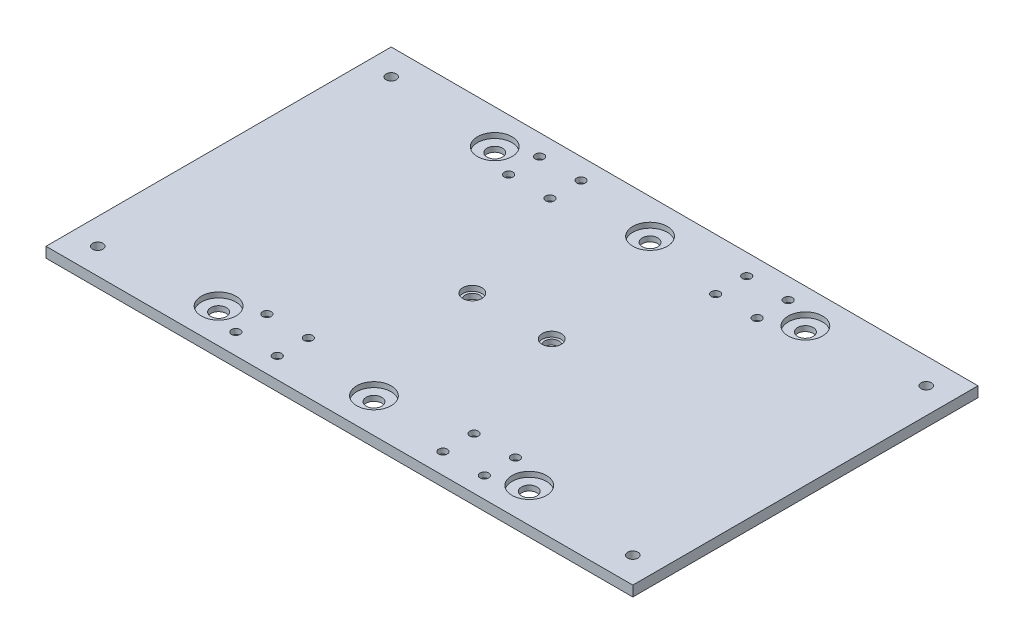
SolidWorks part; units mm, degrees
ref_plane "Front Plane" through (0, 0, 0) normal (0, 0, 1) x (1, 0, 0)
ref_plane "Top Plane" through (0, 0, 0) normal (0, 1, 0) x (1, 0, 0)
ref_plane "Right Plane" through (0, 0, 0) normal (1, 0, 0) x (0, 0, -1)
sketch "Sketch1" plane through (0, 0, 0) normal (0, 1, 0) x (1, 0, 0)
  line L0 (-1000, 0) -> (49000, 0) construction
  line L1 (-170, 100) -> (170, 100)
  line L2 (-170, 100) -> (-170, -100)
  line L3 (-170, -100) -> (170, -100)
  line L4 (170, 100) -> (170, -100)
  line L5 (-170, 100) -> (170, -100) construction
  line L6 (-170, -100) -> (170, 100) construction
  line L7 (0, -1000) -> (0, 49000) construction
  line L8 (60, -1000) -> (60, 49000) construction
  line L9 (-60, -1000) -> (-60, 49000) construction
  line L11 (48, 88) -> (72, 88) construction
  line L12 (48, 88) -> (48, 70) construction
  line L13 (48, 70) -> (72, 70) construction
  line L14 (72, 88) -> (72, 70) construction
  line L15 (48, 88) -> (72, 70) construction
  line L16 (48, 70) -> (72, 88) construction
  circle A0 centre (-23, 0) radius 4.1
  circle A1 centre (23, 0) radius 4.1
  circle A2 centre (72, 88) radius 1.5
  circle A3 centre (48, 88) radius 1.5
  circle A4 centre (72, 70) radius 1.5
  circle A5 centre (48, 70) radius 1.5
  circle A6 centre (-48, 70) radius 1.5
  circle A7 centre (-72, 70) radius 1.5
  circle A8 centre (-48, 88) radius 1.5
  circle A9 centre (-72, 88) radius 1.5
  circle A10 centre (-72, -88) radius 1.5
  circle A11 centre (-48, -88) radius 1.5
  circle A12 centre (-72, -70) radius 1.5
  circle A13 centre (-48, -70) radius 1.5
  circle A14 centre (48, -70) radius 1.5
  circle A15 centre (72, -70) radius 1.5
  circle A16 centre (48, -88) radius 1.5
  circle A17 centre (72, -88) radius 1.5
  circle A18 centre (155, 85) radius 3
  circle A19 centre (-155, 85) radius 3
  circle A20 centre (155, -85) radius 3
  circle A21 centre (-155, -85) radius 3
  circle A23 centre (0, 80) radius 4.5
  circle A24 centre (0, -80) radius 4.5
  circle A25 centre (90, 80) radius 4.5
  circle A26 centre (90, -80) radius 4.5
  circle A27 centre (-90, -80) radius 4.5
  circle A28 centre (-90, 80) radius 4.5
  point P0 (0, 0)
  point P18 (60, 79)
  dimension "D5" = 8.2
  dimension "D6" = 23
  dimension "D10" = 3
  dimension "D12" = 18
  dimension "D15" = 6
  dimension "D16" = 9
  dimension "D17" = 20
  dimension "D19" = 90
  dimension "D1" = 200
  dimension "D2" = 340
  dimension "D7" = 24
  dimension "D8" = 18
  dimension "D9" = 70
  dimension "D13" = 15
  dimension "D14" = 15
  dimension "D3" = 60
  dimension "D4" = 60
  dimension "D11" = 2
  dimension "D18" = 2
extrude "Boss-Extrude1" add sketch "Sketch1" along normal blind 6
sketch "Sketch2" plane through (0, 6, 0) normal (0, 1, 0) x (1, 0, 0)
  line L0 (0, -1000) -> (0, 49000) construction
  line L1 (-1000, 0) -> (49000, 0) construction
  circle A0 centre (72, 88) radius 2.5
  circle A1 centre (48, 88) radius 2.5
  circle A2 centre (48, 70) radius 2.5
  circle A3 centre (72, 70) radius 2.5
  circle A5 centre (-72, 70) radius 2.5
  circle A6 centre (-48, 70) radius 2.5
  circle A7 centre (-48, 88) radius 2.5
  circle A8 centre (-72, 88) radius 2.5
  circle A9 centre (-72, -88) radius 2.5
  circle A10 centre (-48, -88) radius 2.5
  circle A11 centre (-48, -70) radius 2.5
  circle A12 centre (-72, -70) radius 2.5
  circle A13 centre (72, -70) radius 2.5
  circle A14 centre (48, -70) radius 2.5
  circle A15 centre (48, -88) radius 2.5
  circle A16 centre (72, -88) radius 2.5
  circle A17 centre (23, 0) radius 5.5
  circle A19 centre (-23, 0) radius 5.5
  circle A20 centre (0, 80) radius 10
  circle A21 centre (0, -80) radius 10
  circle A22 centre (90, 80) radius 10
  circle A23 centre (90, -80) radius 10
  circle A24 centre (-90, -80) radius 10
  circle A25 centre (-90, 80) radius 10
  dimension "D1" = 5
  dimension "D7" = 11
  dimension "D8" = 20
  dimension "D10" = 90
  dimension "D4" = 18
  dimension "D5" = 24
  dimension "D6" = 30
  dimension "D2" = 2
  dimension "D3" = 2
  dimension "D9" = 2
extrude "Cut-Extrude1" cut sketch "Sketch2" against normal blind 3
